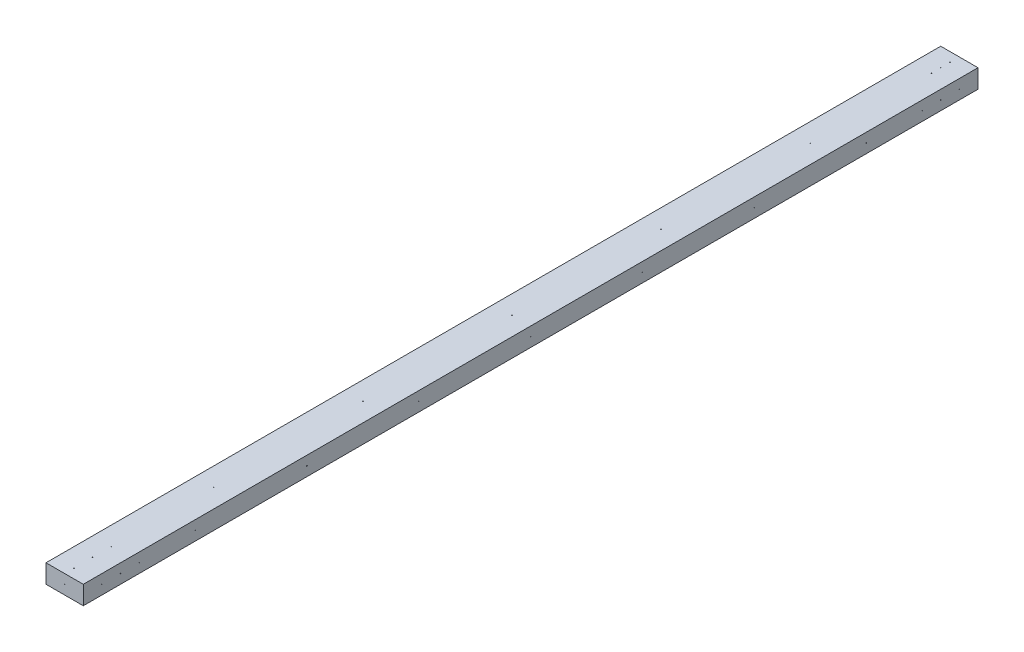
SolidWorks part; units mm, degrees
material "Pine"
ref_plane "Front Plane" through (0, 0, 0) normal (0, 0, 1) x (1, 0, 0)
ref_plane "Top Plane" through (0, 0, 0) normal (0, 1, 0) x (1, 0, 0)
ref_plane "Right Plane" through (0, 0, 0) normal (1, 0, 0) x (0, 0, -1)
sketch "Sketch1" plane through (0, 0, 0) normal (0, 0, 1) x (1, 0, 0)
  line L1 (0, 0) -> (101.6, 0)
  line L2 (0, 0) -> (0, 50.8)
  line L3 (0, 50.8) -> (101.6, 50.8)
  line L4 (101.6, 0) -> (101.6, 50.8)
  dimension "D1" = 101.6
  dimension "D2" = 50.8
extrude "Boss-Extrude1" add sketch "Sketch1" along normal blind 2438.4
sketch "Sketch2" plane through (0, 50.8, 0) normal (0, 1, 0) x (1, 0, 0)
  line L0 (50.8, 0) -> (50.8, -406.4) construction
  line L1 (101.6, 0) -> (0, 0) construction
  line L2 (0, 0) -> (0, -2438.4)
  circle A0 centre (50.8, -406.4) radius 0.8763
  dimension "D2" = 1.7526
  dimension "D1" = 406.4
extrude "Cut-Extrude1" cut sketch "Sketch2" against normal up to surface (50.8 mm away) contours A0 region at (50.8, 50.8, 406.4) up to face at (50.8, 0, 1219.2)
pattern_linear "LPattern1" count 5 spacing 406.4 along (0, 0, 1) of "Cut-Extrude1"
sketch "Sketch3" plane through (0, 50.8, 0) normal (0, 1, 0) x (1, 0, 0)
  line L0 (50.8, 0) -> (50.8, -25.4) construction
  line L1 (101.6, 0) -> (0, 0) construction
  line L2 (101.6, -1219.2) -> (0, -1219.2) construction
  line L3 (101.6, -2438.4) -> (101.6, 0) construction
  line L4 (0, -2438.4) -> (0, 0) construction
  circle A0 centre (50.8, -25.4) radius 0.8763
  circle A1 centre (50.8, -2311.4) radius 0.8763
  circle A2 centre (50.8, -50.8) radius 0.8763
  circle A3 centre (50.8, -76.2) radius 0.8763
  circle A4 centre (50.8, -2362.2) radius 0.8763
  circle A5 centre (50.8, -2413) radius 0.8763
  dimension "D2" = 1.7526
  dimension "D1" = 25.4
  dimension "D3" = 3
extrude "Cut-Extrude2" cut sketch "Sketch3" against normal up to surface (50.8 mm away) up to face at (50.8, 0, 2032.8763)
sketch "Sketch4" plane through (0, 0, 2438.4) normal (0, 0, 1) x (1, 0, 0)
  line L0 (0, 50.8) -> (101.6, 0) construction
  line L1 (101.6, 50.8) -> (0, 0) construction
  circle A0 centre (50.8, 25.4) radius 0.8763
  dimension "D1" = 1.7526
extrude "Cut-Extrude3" cut sketch "Sketch4" against normal up to surface (2438.4 mm away) up to face at (50.8, 25.4, 0)
sketch "Sketch6" plane through (0, 0, 0) normal (-1, 0, 0) x (0, 0, 1)
  line L0 (0, 25.4) -> (304.8, 25.4) construction
  line L1 (0, 50.8) -> (0, 0) construction
  circle A0 centre (304.8, 25.4) radius 0.8763
  circle A1 centre (609.6, 25.4) radius 0.8763
  circle A2 centre (914.4, 25.4) radius 0.8763
  circle A3 centre (1219.2, 25.4) radius 0.8763
  circle A4 centre (1524, 25.4) radius 0.8763
  circle A5 centre (1828.8, 25.4) radius 0.8763
  circle A6 centre (2133.6, 25.4) radius 0.8763
  dimension "D2" = 1.7526
  dimension "D1" = 304.8
  dimension "D3" = 7
extrude "Cut-Extrude4" cut sketch "Sketch6" against normal up to surface (101.6 mm away) up to face at (101.6, 25.4, 1219.2)
sketch "Sketch7" plane through (0, 0, 0) normal (-1, 0, 0) x (0, 0, 1)
  line L0 (0, 25.4) -> (50.8, 25.4) construction
  line L1 (0, 50.8) -> (0, 0) construction
  line L2 (1219.2, 0) -> (1219.2, 50.8) construction
  line L3 (2438.4, 0) -> (0, 0) construction
  line L4 (2438.4, 50.8) -> (0, 50.8) construction
  circle A0 centre (50.8, 25.4) radius 0.8763
  circle A1 centre (101.6, 25.4) radius 0.8763
  circle A2 centre (152.4, 25.4) radius 0.8763
  circle A3 centre (2286, 25.4) radius 0.8763
  circle A4 centre (2336.8, 25.4) radius 0.8763
  circle A5 centre (2387.6, 25.4) radius 0.8763
  dimension "D1" = 1.7526
  dimension "D2" = 50.8
  dimension "D3" = 3
extrude "Cut-Extrude5" cut sketch "Sketch7" against normal up to surface (101.6 mm away) up to face at (101.6, 25.4, 2134.4763)
equation "\"length\"= 1219.2 * 2"
equation "\"D1@Boss-Extrude1\"=\"length\""
equation "\"D1@LPattern1\"=\"length\" / 406.40 - 1"
equation "\"D3@Sketch6\"=\"length\" / 304.8 - 1"
